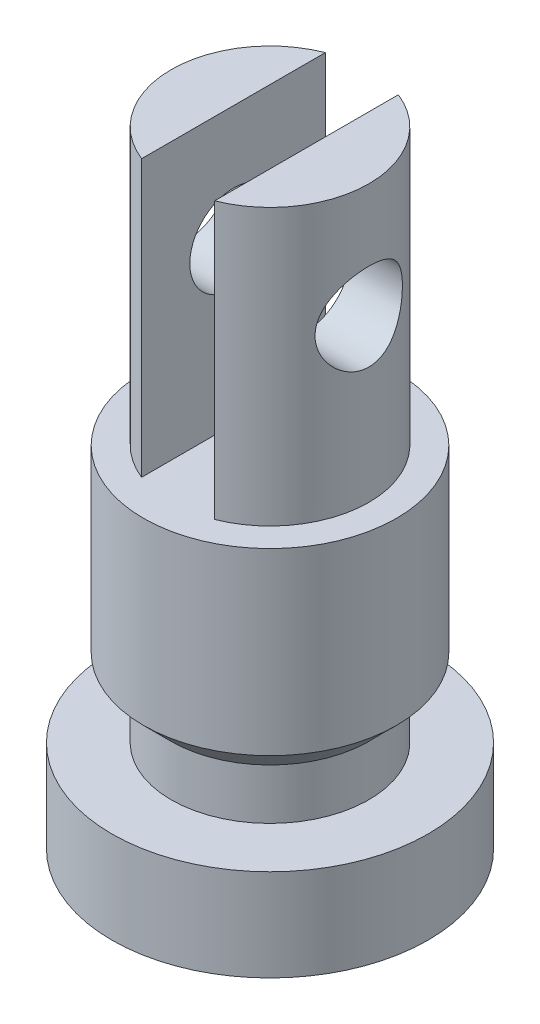
SolidWorks part; units mm, degrees
material "ABS"
ref_plane "Front Plane" through (0, 0, 0) normal (0, 0, 1) x (1, 0, 0)
ref_plane "Top Plane" through (0, 0, 0) normal (0, 1, 0) x (1, 0, 0)
ref_plane "Right Plane" through (0, 0, 0) normal (1, 0, 0) x (0, 0, -1)
sketch "Sketch1" plane through (0, 0, 0) normal (0, 1, 0) x (1, 0, 0)
  circle A0 centre (0, 0) radius 6.875
  dimension "D1" = 13.75
extrude "Boss-Extrude1" add sketch "Sketch1" along normal blind 4
sketch "Sketch8" plane through (0, 4, 0) normal (0, 1, 0) x (1, 0, 0)
  circle A0 centre (0, 0) radius 4.3
  dimension "D1" = 8.6
extrude "Boss-Extrude4" add sketch "Sketch8" along normal blind 2.2
sketch "Sketch2" plane through (0, 6.2, 0) normal (0, 1, 0) x (1, 0, 0)
  circle A2 centre (0, 0) radius 5.5
  point P0 (0, 0)
  dimension "D1" = 11
extrude "Boss-Extrude2" add sketch "Sketch2" along normal blind 9
sketch "Sketch3" plane through (0, 15.2, 0) normal (0, 1, 0) x (1, 0, 0)
  circle A0 centre (0, 0) radius 4.3
  dimension "D1" = 8.6
extrude "Boss-Extrude3" add sketch "Sketch3" along normal blind 12
sketch "Sketch4" plane through (0, 27.2, 0) normal (0, 1, 0) x (1, 0, 0)
  line L1 (-1.5875, 4.3) -> (1.5875, 4.3)
  line L2 (-1.5875, 4.3) -> (-1.5875, -4.3)
  line L3 (-1.5875, -4.3) -> (1.5875, -4.3)
  line L4 (1.5875, 4.3) -> (1.5875, -4.3)
  line L5 (-1.5875, 4.3) -> (1.5875, -4.3) construction
  line L6 (-1.5875, -4.3) -> (1.5875, 4.3) construction
  point P0 (0, 0)
  dimension "D1" = 8.6
  dimension "D2" = 3.175
extrude "Cut-Extrude1" cut sketch "Sketch4" against normal blind 12
sketch "Sketch5" plane through (1.5875, 0, 0) normal (-1, 0, 0) x (0, 0, 1)
  line L0 (3.9962, 15.2) -> (-3.9962, 15.2) construction
  line L1 (3.9962, 27.2) -> (-3.9962, 27.2) construction
  line L2 (3.9962, 15.2) -> (-3.9962, 15.2)
  line L3 (3.9962, 27.2) -> (-3.9962, 27.2)
  line L4 (0, 15.2) -> (0, 22.2) construction
  circle A0 centre (0, 22.2) radius 1.9
  dimension "D2" = 3.8
  dimension "D1" = 7
extrude "Cut-Extrude2" cut sketch "Sketch5" against normal through all both and the other way through all contours A0
chamfer "Chamfer1" distance 1.2 angle 45 1 edges at (0, 6.2, 5.5)
equation "\"prop-dist\"= 80mm"
equation "\"prop-hole-depth\"= 9mm"
equation "\"prop-hole-diameter\"= 11mm"
equation "\"rivet-extension\" = 12mm"
equation "\"rivet-hole-extension\"= 7mm"
equation "\"rivet-hole-diameter\"= 3.8mm"
equation "\"ski-length\"= 100mm"
equation "\"th\"= 0.125in'material thickness"
equation "\"ski-height\"= 30mm"
equation "\"ski-curve-gap\"= 60mm"
equation "\"ski-curve-height\"= \"rivet-hole-extension\""
equation "\"min-width\"= 4mm"
equation "\"prop-hole-diameter-small\"= 8.6mm"
equation "\"D1@Sketch1\"=\"prop-hole-diameter\"*1.25"
equation "\"D1@Sketch2\"=\"prop-hole-diameter\""
equation "\"D1@Boss-Extrude2\"=\"prop-hole-depth\""
equation "\"D1@Sketch3\"=\"prop-hole-diameter-small\""
equation "\"D1@Boss-Extrude3\"=\"rivet-extension\""
equation "\"D1@Sketch4\"=\"prop-hole-diameter-small\""
equation "\"D2@Sketch4\"=\"th\""
equation "\"D1@Cut-Extrude1\"=\"rivet-extension\""
equation "\"D1@Sketch5\"=\"rivet-hole-extension\""
equation "\"D2@Sketch5\"=\"rivet-hole-diameter\""
equation "\"D1@Sketch8\"=\"prop-hole-diameter-small\""
equation "\"D1@Chamfer1\"=(\"prop-hole-diameter\"-\"prop-hole-diameter-small\")/2"
